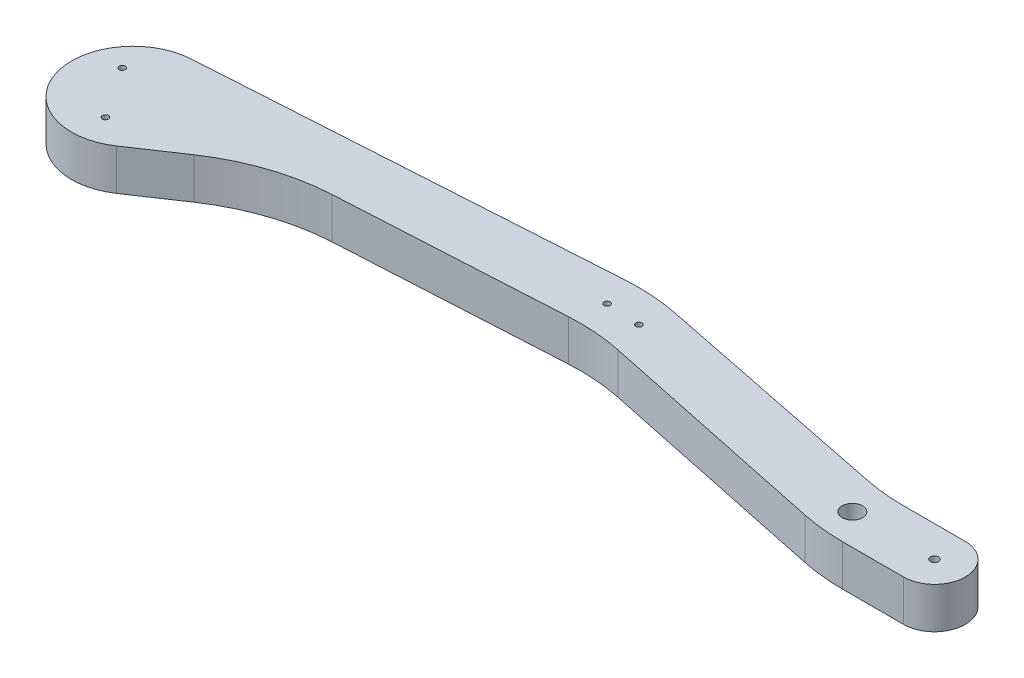
SolidWorks part; units mm, degrees
ref_plane "Front Plane" through (0, 0, 0) normal (0, 0, 1) x (1, 0, 0)
ref_plane "Top Plane" through (0, 0, 0) normal (0, 1, 0) x (1, 0, 0)
ref_plane "Right Plane" through (0, 0, 0) normal (1, 0, 0) x (0, 0, -1)
sketch "Sketch1" plane through (0, 0, 0) normal (0, 1, 0) x (1, 0, 0)
  line L0 (0, 0) -> (-350, 0) construction
  line L1 (0, 0) -> (40, 0) construction
  line L2 (0, 15) -> (40, 15)
  line L3 (0, -15) -> (40, -15)
  line L4 (-351.8754, 29.9413) -> (-333.2857, -24.9125) construction
  line L5 (-139.7849, 43.2259) -> (-4217.6379, -212.1962)
  line L6 (0, 15) -> (-4004.6012, 823.6244)
  line L7 (0, 15) -> (-5.9197, -13.7825) construction
  line L8 (-4217.6379, -212.1962) -> (-138.0533, 13.889)
  line L9 (-4004.6012, 823.6244) -> (-5.9197, -13.7825)
  line L10 (-333.2857, -24.9125) -> (-287.8235, 5.5889)
  line L11 (-5.9197, -13.7825) -> (0, -15)
  circle A0 centre (0, 0) radius 5
  circle A1 centre (-350, 0) radius 30
  circle A2 centre (40, 0) radius 2
  circle A3 centre (0, 0) radius 15
  circle A4 centre (40, 0) radius 15
  dimension "D1" = 10
  dimension "D4" = 4
  dimension "D5" = 60
  dimension "D6" = 30
  dimension "D7" = 165
  dimension "D2" = 350
  dimension "D3" = 40
  dimension "D8" = 165
  dimension "D9" = 135
  dimension "D10" = 150
extrude "Boss-Extrude1" add sketch "Sketch1" along normal blind 10 and the other way blind 10 contours L8 A1 | A1 L8 | A1 L8 L9 L5 | A1 L10 L8 | A3 L6 L5 L9 | A3 A0 | A4 L2 A3 L3 | A4 A2 region at (-104.3815, 0, -20.1768) region at (20, 0, 0) region at (10.3066, 0, -10.3066) region at (50.3066, 0, -10.3066) region at (-256.3648, 0, -20.0554) region at (-350.7689, 0, -13.8751) region at (-310.7553, 0, 3.5404) region at (-349.359, 0, 11.5664)
fillet "Fillet1" radius 100 5 edges at (0, 0, -15) (-139.7849, 0, -43.2259) (-138.0533, 0, -13.889) (-287.8235, 0, -5.5889) (0, 0, 15)
sketch "Sketch2" plane through (0, 10, 0) normal (0, 1, 0) x (1, 0, 0)
  circle A0 centre (-147.3362, 28.0506) radius 1.5
  circle A1 centre (-130.7919, 26.9057) radius 1.5
  circle A2 centre (-364.7467, 9.4158) radius 1.5
  circle A3 centre (-348.0325, -15.4967) radius 1.5
extrude "Cut-Extrude1" cut sketch "Sketch2" against normal blind 10
